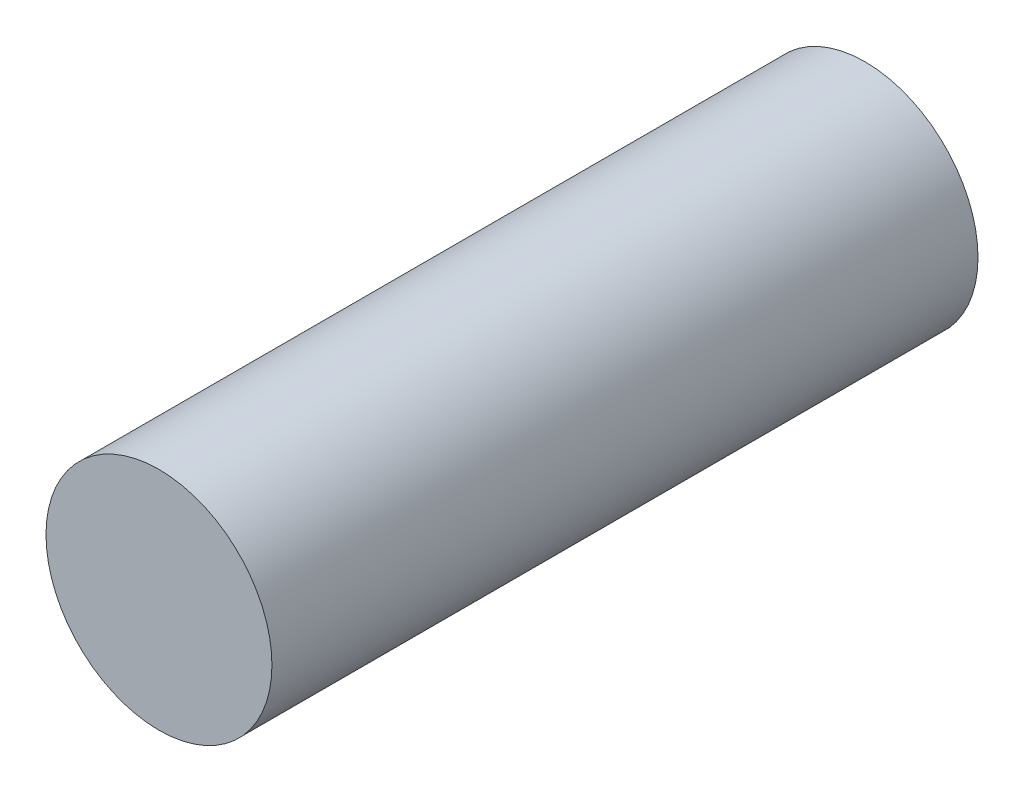
SolidWorks part; units mm, degrees
material "1060 Alloy"
ref_plane "Front Plane" through (0, 0, 0) normal (0, 0, 1) x (1, 0, 0)
ref_plane "Top Plane" through (0, 0, 0) normal (0, 1, 0) x (1, 0, 0)
ref_plane "Right Plane" through (0, 0, 0) normal (1, 0, 0) x (0, 0, -1)
sketch "Sketch1" plane through (0, 0, 0) normal (0, 0, 1) x (1, 0, 0)
  circle A0 centre (-36.8615, 18.4744) radius 4
  dimension "D1" = 8
extrude "Boss-Extrude1" add sketch "Sketch1" along normal blind 25
